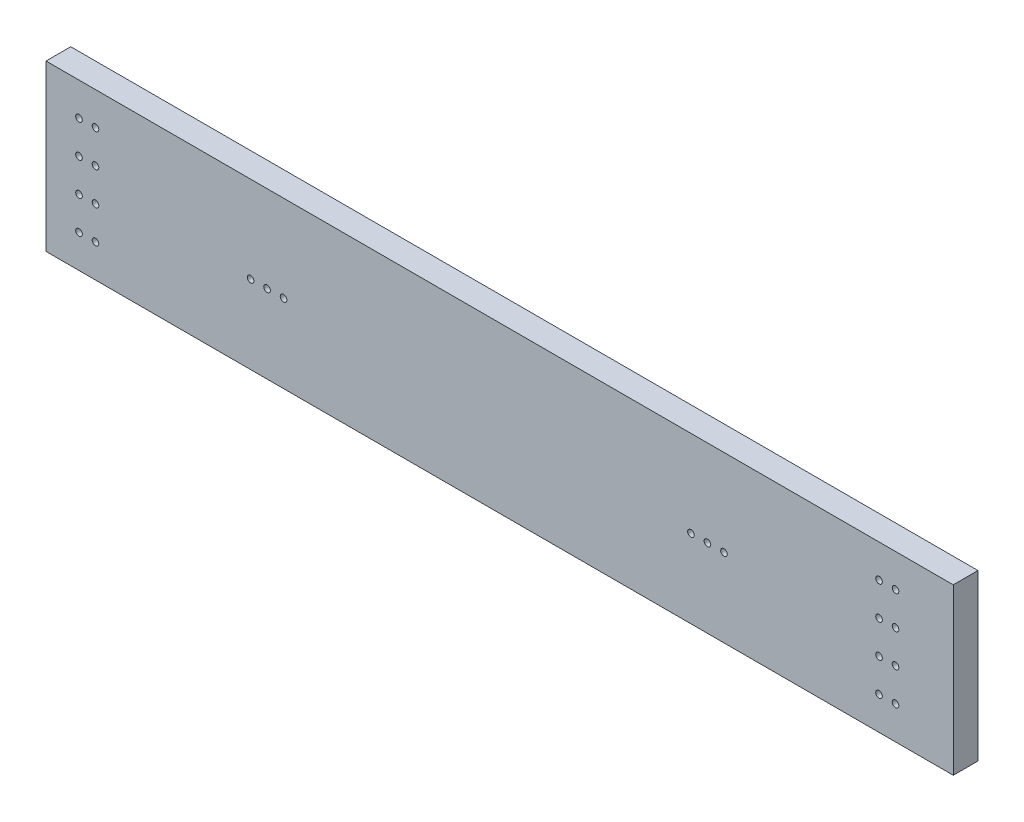
SolidWorks part; units mm, degrees
material "Pine"
ref_plane "Front Plane" through (0, 0, 0) normal (0, 0, 1) x (1, 0, 0)
ref_plane "Top Plane" through (0, 0, 0) normal (0, 1, 0) x (1, 0, 0)
ref_plane "Right Plane" through (0, 0, 0) normal (1, 0, 0) x (0, 0, -1)
sketch "Sketch1" plane through (0, 0, 0) normal (0, 0, 1) x (1, 0, 0)
  line L1 (-349.25, -63.5) -> (349.25, -63.5)
  line L2 (-349.25, -63.5) -> (-349.25, 63.5)
  line L3 (-349.25, 63.5) -> (349.25, 63.5)
  line L4 (349.25, -63.5) -> (349.25, 63.5)
  line L5 (-349.25, -63.5) -> (349.25, 63.5) construction
  line L6 (-349.25, 63.5) -> (349.25, -63.5) construction
  point P0 (0, 0)
  dimension "D1" = 698.5
  dimension "D2" = 127
extrude "Boss-Extrude1" add sketch "Sketch1" along normal blind 19.05
sketch "Sketch2" plane through (0, 0, 19.05) normal (0, 0, 1) x (1, 0, 0)
  line L0 (349.25, -63.5) -> (349.25, 63.5) construction
  line L1 (349.25, 63.5) -> (-349.25, 63.5) construction
  line L2 (-9.525, 63.5) -> (-9.525, -63.5) construction
  line L3 (-349.25, 63.5) -> (-349.25, -63.5) construction
  line L4 (-349.25, 63.5) -> (349.25, 63.5) construction
  line L5 (-349.25, -63.5) -> (349.25, -63.5) construction
  circle A1 centre (304.8, 38.1) radius 2.54
  circle A2 centre (304.8, 12.7) radius 2.54
  circle A3 centre (304.8, -12.7) radius 2.54
  circle A4 centre (304.8, -38.1) radius 2.54
  circle A5 centre (292.1, -38.1) radius 2.54
  circle A6 centre (292.1, -12.7) radius 2.54
  circle A7 centre (292.1, 12.7) radius 2.54
  circle A8 centre (292.1, 38.1) radius 2.54
  circle A9 centre (-323.85, 38.1) radius 2.54
  circle A10 centre (-311.15, 38.1) radius 2.54
  circle A11 centre (-323.85, 12.7) radius 2.54
  circle A12 centre (-311.15, 12.7) radius 2.54
  circle A13 centre (-323.85, -12.7) radius 2.54
  circle A14 centre (-311.15, -12.7) radius 2.54
  circle A15 centre (-323.85, -38.1) radius 2.54
  circle A16 centre (-311.15, -38.1) radius 2.54
  circle A17 centre (147.32, -3.175) radius 2.54
  circle A18 centre (160.02, -3.175) radius 2.54
  circle A19 centre (172.72, -3.175) radius 2.54
  circle A20 centre (-191.77, -3.175) radius 2.54
  circle A21 centre (-179.07, -3.175) radius 2.54
  circle A22 centre (-166.37, -3.175) radius 2.54
  dimension "D1" = 5.08
  dimension "D8" = 5.08
  dimension "D15" = 5.08
  dimension "D21" = 5.08
  dimension "D24" = 339.725
  dimension "D2" = 44.45
  dimension "D3" = 12.7
  dimension "D4" = 25.4
  dimension "D5" = 25.4
  dimension "D6" = 25.4
  dimension "D7" = 25.4
  dimension "D9" = 25.4
  dimension "D10" = 25.4
  dimension "D11" = 25.4
  dimension "D12" = 25.4
  dimension "D13" = 25.4
  dimension "D14" = 12.7
  dimension "D16" = 12.7
  dimension "D17" = 12.7
  dimension "D18" = 313.69
  dimension "D19" = 66.675
  dimension "D20" = 66.675
  dimension "D22" = 12.7
  dimension "D23" = 12.7
  dimension "D25" = 156.845
extrude "Cut-Extrude1" cut sketch "Sketch2" against normal through all
